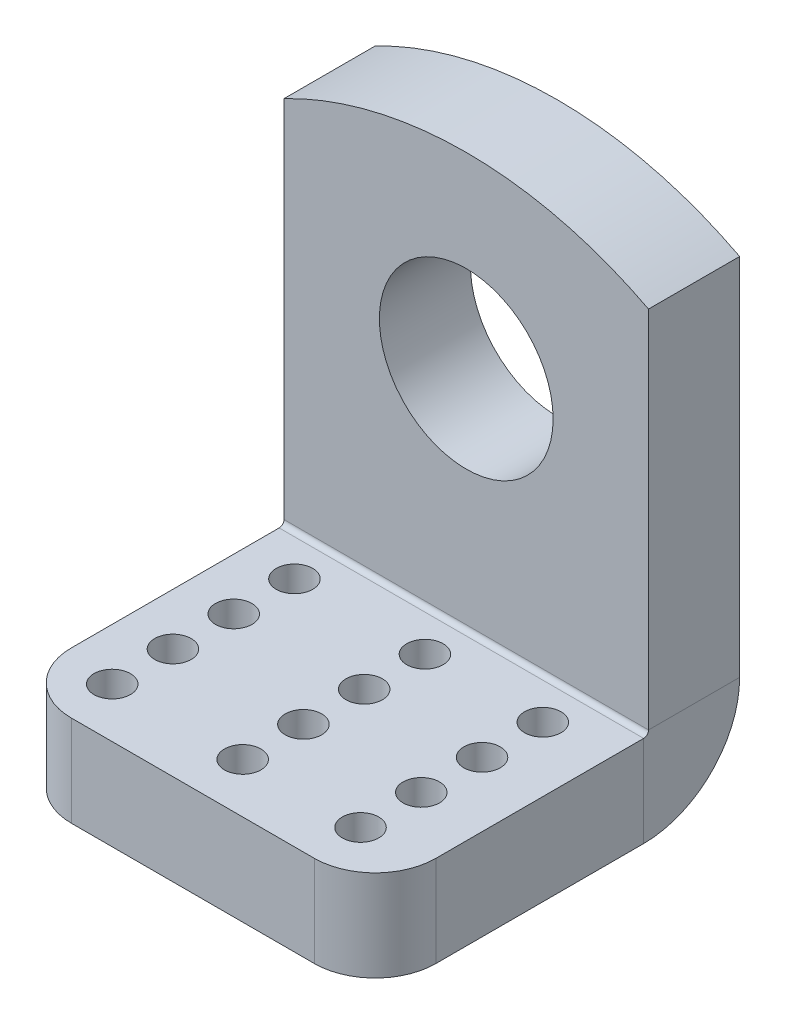
SolidWorks part; units mm, degrees
note: The reader was unsure of these and kept them because the rebuilt part matched: flange length of "Edge-Flange1".
ref_plane "Front Plane" through (0, 0, 0) normal (0, 0, 1) x (1, 0, 0)
ref_plane "Top Plane" through (0, 0, 0) normal (0, 1, 0) x (1, 0, 0)
ref_plane "Right Plane" through (0, 0, 0) normal (1, 0, 0) x (0, 0, -1)
sketch "Sketch1" plane through (0, 0, 0) normal (0, 0, 1) x (1, 0, 0)
  line L0 (-30, 0) -> (30, 0)
  line L1 (-30, 0) -> (-30, 60)
  line L2 (30, 0) -> (30, 60)
  arc A0 (-30, 60) -> (30, 60) centre (0, 2.3372) cw
  circle A1 centre (0, 36.48) radius 14.3
  dimension "D3" = 65
  dimension "D4" = 28.6
  dimension "D5" = 36.48
  dimension "D1" = 60
  dimension "D2" = 60
base flange "Base-Flange1" sketch "Sketch1" thickness 15 reverse thickness direction no parameters "D1"=0.8
edge flange "Edge-Flange1" sketch "Sketch8" flange angle 90 flange length 60 flange position bend outside bend radius 0.8 thickness 15 parameters "D6"=10
sketch "Sketch8" plane through (0, 0, 0) normal (0, -1, 0) x (1, 0, 0)
  line L0 (-30, 0) -> (30, 0) construction
  line L1 (-30, 0) -> (30, 0)
  line L2 (-30, 0) -> (-30, 45)
  line L3 (-30, 45) -> (30, 45)
  line L4 (30, 45) -> (30, 0)
bend "EdgeBend1" bend radius 0.8 bend angle 90 parameters "D5"=1
sketch "Sketch9" plane through (0, -0.8, 0) normal (0, 1, 0) x (1, 0, 0)
  line L0 (-21.4781, -0.8) -> (-21.4781, -45) construction
  line L1 (-30, -0.8) -> (30, -0.8) construction
  line L2 (30, -45) -> (-30, -45) construction
  line L3 (19.3983, -0.8) -> (19.3983, -45) construction
  line L4 (0, -0.8) -> (0, -45) construction
  circle A0 centre (-21.4781, -6.8007) radius 3
  circle A1 centre (19.3983, -6.8007) radius 3
  circle A2 centre (0, -6.8007) radius 3
  circle A3 centre (-21.4781, -16.8007) radius 3
  circle A4 centre (-21.4781, -26.8007) radius 3
  circle A5 centre (-21.4781, -36.8007) radius 3
  circle A6 centre (0, -16.8007) radius 3
  circle A7 centre (0, -26.8007) radius 3
  circle A8 centre (0, -36.8007) radius 3
  circle A9 centre (19.3983, -16.8007) radius 3
  circle A10 centre (19.3983, -26.8007) radius 3
  circle A11 centre (19.3983, -36.8007) radius 3
  dimension "D1" = 6
  dimension "D2" = 4
  dimension "D3" = 4
  dimension "D4" = 4
extrude "Cut-Extrude1" cut sketch "Sketch9" against normal blind 50
fillet "Fillet1" radius 10 2 edges at (30, -8.3, 45) (-30, -8.3, 45)
sketch "Bend-Lines1" [suppressed] plane through (0, 0, 0) normal (0, 1, 0) x (1, 0, 0)
sketch "Bounding-Box1" [suppressed] plane through (0, 0, 0) normal (0, 1, 0) x (1, 0, 0)
sheet metal parameters "Sheet-Metal2" thickness 15 parameters "D1"=0.8
flat pattern "Flat-Pattern2" [suppressed]
sketch "Bend-Lines2" plane through (0, 0, 0) normal (0, 1, 0) x (1, 0, 0)
sketch3d "Bounding-Box2" [suppressed]
  line L0 (-45, -42.0958, 0) -> (-45, 65, 0) construction
  line L1 (45, -42.0958, 0) -> (45, 65, 0) construction
  line L2 (-45, -42.0958, 0) -> (45, -42.0958, 0) construction
  line L3 (-45, 65, 0) -> (45, 65, 0) construction
sheet metal parameters "Sheet-Metal3" thickness 15 parameters "D1"=0.8
flat pattern "Flat-Pattern2"
sketch "Bend-Lines2" plane through (0, 0, 0) normal (0, 0, 1) x (1, 0, 0)
  line L0 (-30, -6.5188) -> (30, -6.5188) construction
  line L1 (-30, -6.5188) -> (30, -6.5188) construction
sketch3d "Bounding-Box2" [suppressed]
  line L0 (30, 65, 0) -> (30, -59.5748, 0) construction
  line L1 (-30, 65, 0) -> (-30, -59.5748, 0) construction
  line L2 (30, 65, 0) -> (-30, 65, 0) construction
  line L3 (30, -59.5748, 0) -> (-30, -59.5748, 0) construction
bend of the flat pattern "Flatten-<EdgeBend1>1"
sheet metal parameters "Sheet-Metal4" thickness 15 parameters "D1"=0.8
flat pattern "Flat-Pattern2"
sketch "Bend-Lines2" plane through (0, 0, 0) normal (0, 0, 1) x (1, 0, 0)
  line L0 (-30, -6.5188) -> (30, -6.5188) construction
  line L1 (-30, -6.5188) -> (30, -6.5188) construction
sketch3d "Bounding-Box2" [suppressed]
  line L0 (30, 65, 0) -> (30, -59.5748, 0) construction
  line L1 (-30, 65, 0) -> (-30, -59.5748, 0) construction
  line L2 (30, 65, 0) -> (-30, 65, 0) construction
  line L3 (30, -59.5748, 0) -> (-30, -59.5748, 0) construction
bend of the flat pattern "Flatten-<EdgeBend1>1"
